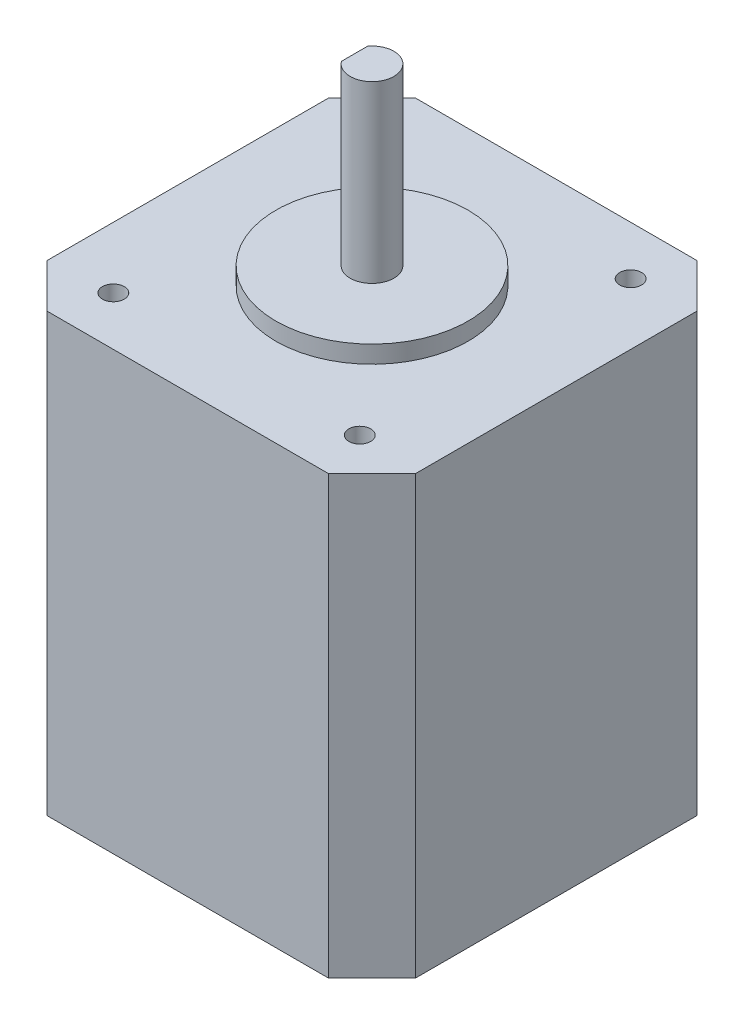
SolidWorks part; units mm, degrees
ref_plane "前视基准面" through (0, 0, 0) normal (0, 0, 1) x (1, 0, 0)
ref_plane "上视基准面" through (0, 0, 0) normal (0, 1, 0) x (1, 0, 0)
ref_plane "右视基准面" through (0, 0, 0) normal (1, 0, 0) x (0, 0, -1)
sketch "草图1" plane through (0, 0, 0) normal (0, 1, 0) x (1, 0, 0)
  line L0 (0, 74.4301) -> (0, -75.3699) construction
  line L1 (-87.211, 0) -> (85.3315, 0) construction
  line L2 (-16.1, -21.1) -> (16.1, -21.1)
  line L3 (-21.1, 16.1) -> (-21.1, -16.1)
  line L4 (-16.1, 21.1) -> (16.1, 21.1)
  line L5 (21.1, 16.1) -> (21.1, -16.1)
  line L6 (-15.5, 74.4301) -> (-15.5, -75.3699) construction
  line L7 (-87.211, -15.5) -> (85.3315, -15.5) construction
  line L8 (15.5, 74.4301) -> (15.5, -75.3699) construction
  line L9 (-87.211, 15.5) -> (85.3315, 15.5) construction
  line L10 (-87.211, 21.1) -> (85.3315, 21.1) construction
  line L11 (-21.1, 74.4301) -> (-21.1, -75.3699) construction
  line L12 (-21.1, 16.1) -> (-16.1, 21.1)
  line L13 (21.1, 74.4301) -> (21.1, -75.3699) construction
  line L14 (16.1, 21.1) -> (21.1, 16.1)
  line L15 (-87.211, -21.1) -> (85.3315, -21.1) construction
  line L16 (21.1, -16.1) -> (16.1, -21.1)
  line L17 (-21.1, -16.1) -> (-16.1, -21.1)
  line L21 (-2, 1.5) -> (-2, -1.5)
  circle A4 centre (0, 0) radius 11
  circle A5 centre (0, 0) radius 2.5
  circle A6 centre (-14.1, 15.5) radius 1.25
  circle A7 centre (14.1, 15.5) radius 1.25
  circle A8 centre (14.1, -15.5) radius 1.25
  circle A9 centre (-14.1, -15.5) radius 1.25
  point P23 (-21.1, 21.1)
  point P26 (21.1, 21.1)
  point P29 (21.1, -21.1)
  point P32 (-21.1, -21.1)
  dimension "D11" = 22
  dimension "D12" = 5
  dimension "D15" = 2.5
  dimension "D1" = 21.1
  dimension "D13" = 2
  dimension "D14" = 28.2
  dimension "D2" = 21.1
  dimension "D3" = 15.5
  dimension "D4" = 15.5
extrude "凸台-拉伸1" add sketch "草图1" along normal blind 50 contours L3 L17 L2 L16 L5 L14 L4 L12 A4 A9 A8 region at (-18.178, 0, 18.178)
extrude "凸台-拉伸2" add sketch "草图1<3>" along normal blind 52 contours A4 A5 region at (-10.6889, 0, 0)
sketch "草图1<3>" plane through (0, 0, 0) normal (0, 1, 0) x (1, 0, 0) same geometry as "草图1"
extrude "凸台-拉伸3" add sketch "草图1<4>" along normal blind 72 contours L21 A5 region at (0.1209, 0, 0)
sketch "草图1<4>" plane through (0, 0, 0) normal (0, 1, 0) x (1, 0, 0) same geometry as "草图1"
extrude "凸台-拉伸4" add sketch "草图1<5>" along normal blind 57 contours L21 A5 region at (-2.2018, 0, 0)
sketch "草图1<5>" plane through (0, 0, 0) normal (0, 1, 0) x (1, 0, 0) same geometry as "草图1"
sketch "草图2" plane through (0, 0, -21.1) normal (0, 0, -1) x (-1, 0, 0)
  line L0 (-16.1, 0) -> (16.1, 0)
  line L1 (-16.1, 9) -> (16.1, 9)
  line L2 (0, 14.1622) -> (0, -8.6857)
  line L3 (-10, 14.1622) -> (-10, -8.6857)
  line L4 (10, 14.1622) -> (10, -8.6857)
  dimension "D1" = 9
  dimension "D2" = 10
  dimension "D3" = 10
extrude "凸台-拉伸5" add sketch "草图2" along normal blind 6 contours L4 L1 L2 L0 | L1 L3 L0 L2 region at (5, 4.5, -21.1) region at (-5, 4.5, -21.1)
